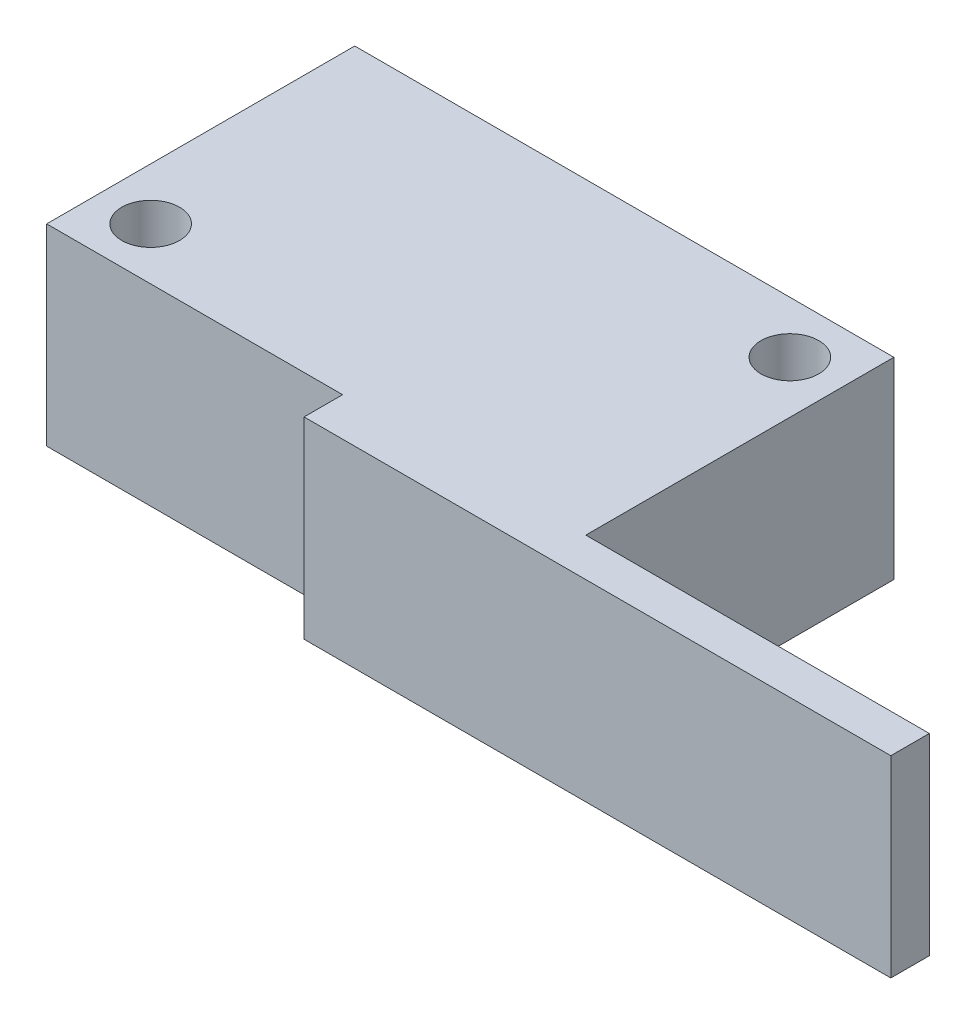
SolidWorks part; units mm, degrees
ref_plane "Front Plane" through (0, 0, 0) normal (0, 0, 1) x (1, 0, 0)
ref_plane "Top Plane" through (0, 0, 0) normal (0, 1, 0) x (1, 0, 0)
ref_plane "Right Plane" through (0, 0, 0) normal (1, 0, 0) x (0, 0, -1)
sketch "Sketch1" plane through (0, 0, 0) normal (0, 1, 0) x (1, 0, 0)
  line L1 (-14, 8) -> (14, 8)
  line L2 (-14, 8) -> (-14, -8)
  line L3 (-14, -8) -> (14, -8)
  line L4 (14, 8) -> (14, -8)
  line L5 (-14, 8) -> (14, -8) construction
  line L6 (-14, -8) -> (14, 8) construction
  point P0 (0, 0)
  dimension "D1" = 16
  dimension "D2" = 28
extrude "Boss-Extrude1" add sketch "Sketch1" along normal blind 10
sketch "Sketch2" plane through (0, 10, 0) normal (0, 1, 0) x (1, 0, 0)
  line L0 (14, 8) -> (-14, 8) construction
  line L2 (14, -8) -> (14, 8) construction
  line L3 (-14, 8) -> (-14, -8) construction
  line L4 (-14, -8) -> (14, -8) construction
  circle A0 centre (-11.3, -5.3) radius 1.5
  circle A1 centre (11.3, 5.3) radius 1.5
  point P4 (11.5172, 5.6958)
  point P9 (14, 6.3019)
  point P10 (-11.0903, -5.6782)
  dimension "D1" = 3
  dimension "D2" = 3
  dimension "D3" = 2.7
  dimension "D4" = 2.7
  dimension "D5" = 2.7
  dimension "D6" = 2.7
extrude "Cut-Extrude1" cut sketch "Sketch2" against normal up to next
sketch "Sketch3" plane through (0, 0, 8) normal (0, 0, 1) x (1, 0, 0)
  line L0 (-14, 10) -> (14, 10) construction
  line L1 (1.3682, 10) -> (31.842, 10)
  line L2 (1.3682, 10) -> (1.3682, 0)
  line L3 (1.3682, 0) -> (31.842, 0)
  line L4 (31.842, 10) -> (31.842, 0)
extrude "Boss-Extrude2" add sketch "Sketch3" along normal blind 2
